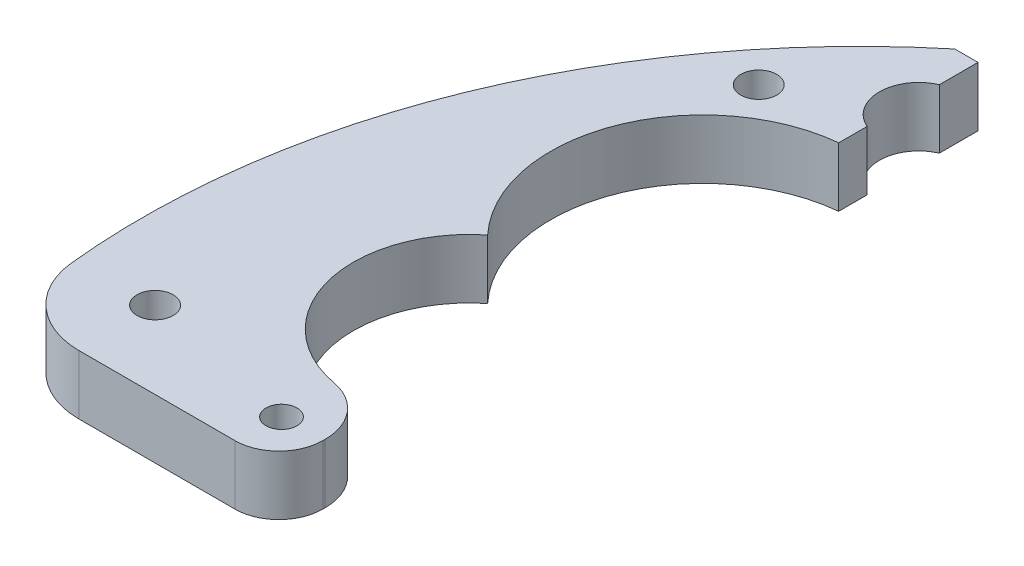
SolidWorks part; units mm, degrees
ref_plane "Front Plane" through (0, 0, 0) normal (0, 0, 1) x (1, 0, 0)
ref_plane "Top Plane" through (0, 0, 0) normal (0, 1, 0) x (1, 0, 0)
ref_plane "Right Plane" through (0, 0, 0) normal (1, 0, 0) x (0, 0, -1)
sketch "Sketch1" plane through (0, 0, 0) normal (0, 1, 0) x (1, 0, 0)
  line L0 (30.3798, 69.405) -> (32.6658, 69.405)
  line L1 (32.6658, 69.405) -> (32.6658, 0.571)
  line L5 (32.6658, 0.571) -> (6.2498, 0.571)
  arc A0 (6.2498, 0.571) -> (30.3798, 69.405) centre (75.3749, 14.9854) cw
  point P4 (30.3798, 69.405)
  dimension "D1" = 26.416
  dimension "D2" = 68.834
  dimension "D3" = 2.286
extrude "Boss-Extrude1" add sketch "Sketch1" along normal blind 5.842
sketch "Sketch2" plane through (0, 5.842, 0) normal (0, 1, 0) x (1, 0, 0)
  line L0 (32.6658, 0.571) -> (32.6658, 69.405) construction
  line L1 (32.6658, 65.595) -> (32.6658, 58.483)
  arc A0 (32.6658, 58.483) -> (32.6658, 65.595) centre (34.1898, 62.039) cw
  point P0 (32.6658, 65.595)
  point P1 (32.6658, 58.483)
  dimension "D3" = 1.524
  dimension "D1" = 3.81
  dimension "D2" = 7.112
extrude "Cut-Extrude1" cut sketch "Sketch2" against normal through all
sketch "Sketch7" plane through (0, 5.842, 0) normal (0, 1, 0) x (1, 0, 0)
  line L1 (32.6658, 0.571) -> (32.6658, 58.483) construction
  line L2 (34.1898, 0.571) -> (34.1898, 58.483)
  line L3 (34.1898, 0.571) -> (34.1898, 58.483) construction
  line L4 (32.6658, 55.689) -> (32.6658, 25.8724)
  arc A0 (32.6658, 55.689) -> (32.6658, 25.8724) centre (34.1898, 40.7807) ccw
  dimension "D2" = 2.794
  dimension "D3" = 14.986
  dimension "D1" = 1.524
extrude "Cut-Extrude2" cut sketch "Sketch7" against normal through all
sketch "Sketch8" plane through (0, 5.842, 0) normal (0, 1, 0) x (1, 0, 0)
  line L2 (32.6658, 30.543) -> (0, 30.543) construction
  line L3 (32.6658, 30.543) -> (30.3798, 30.543)
  line L4 (32.6658, 30.543) -> (30.3798, 30.543) construction
  line L8 (30.3798, 0.571) -> (30.3798, 25.8724)
  line L9 (30.3798, 0.571) -> (30.3798, 25.8724) construction
  circle A0 centre (30.3798, 21.6126) radius 11.43
  arc A1 (32.6658, 55.689) -> (32.6658, 25.8724) centre (34.1898, 40.7807) ccw construction
  point P4 (23.2459, 30.543)
  point P13 (32.6658, 9.969)
  dimension "D1" = 2.286
  dimension "D2" = 22.86
  dimension "D3" = 38.862
extrude "Cut-Extrude3" cut sketch "Sketch8" against normal through all
fillet "Fillet1" radius 7.874 1 edges at (6.2498, 2.921, -0.571)
fillet "Fillet2" radius 4.318 1 edges at (32.6658, 2.921, -0.571)
fillet "Fillet4" radius 5.334 1 edges at (32.6658, 2.921, -10.4135)
sketch "Sketch9" plane through (0, 5.842, 0) normal (0, 1, 0) x (1, 0, 0)
  circle A0 centre (23.7758, 56.705) radius 1.7748
  dimension "D1" = 8.89
  dimension "D2" = 1.016
extrude "Cut-Extrude4" cut sketch "Sketch9" against normal through all
sketch "Sketch10" plane through (0, 5.842, 0) normal (0, 1, 0) x (1, 0, 0)
  circle A0 centre (28.6018, 4.889) radius 1.524
  dimension "D1" = 3.048
  dimension "D2" = 4.064
  dimension "D3" = 4.318
extrude "Cut-Extrude5" cut sketch "Sketch10" against normal through all
sketch "Sketch11" plane through (0, 5.842, 0) normal (0, 1, 0) x (1, 0, 0)
  line L0 (12.9788, 0.571) -> (28.3478, 0.571) construction
  circle A0 centre (12.8538, 8.191) radius 1.778
  dimension "D1" = 3.556
  dimension "D2" = 19.812
  dimension "D3" = 7.62
extrude "Cut-Extrude6" cut sketch "Sketch11" against normal through all
